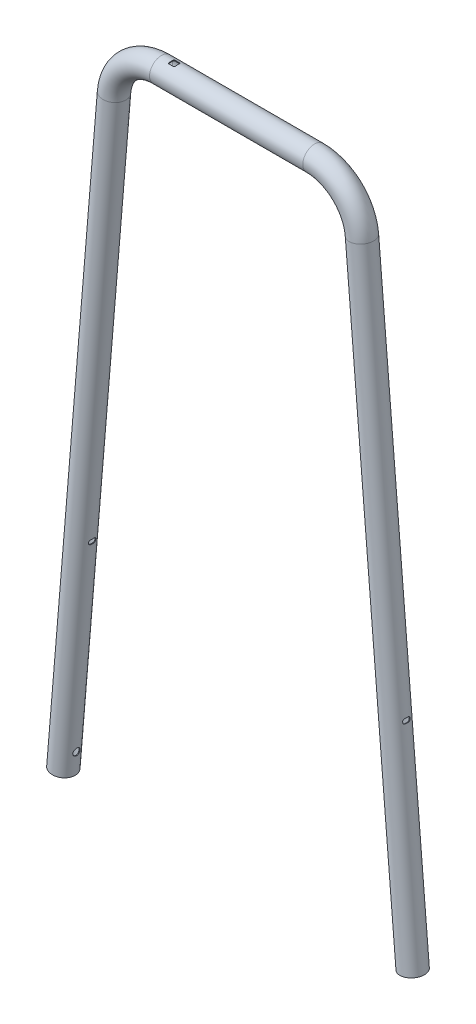
SolidWorks part; units mm, degrees
ref_plane "Front Plane" through (0, 0, 0) normal (0, 0, 1) x (1, 0, 0)
ref_plane "Top Plane" through (0, 0, 0) normal (0, 1, 0) x (1, 0, 0)
ref_plane "Right Plane" through (0, 0, 0) normal (1, 0, 0) x (0, 0, -1)
sketch "Sketch1" plane through (0, 0, 0) normal (0, 0, 1) x (1, 0, 0)
  line L0 (0, 0) -> (0, 595.2821) construction
  line L1 (0, 0) -> (414.971, 0) construction
  line L2 (-85.4711, 567.016) -> (85.4711, 567.016)
  line L3 (138.2891, 518.4048) -> (194.85, -162.284)
  line L4 (-138.2891, 518.4048) -> (-194.85, -162.284)
  line L5 (-194.85, -162.284) -> (-299.6948, -162.284) construction
  arc A0 (138.2891, 518.4048) -> (85.4711, 567.016) centre (85.4711, 514.016) ccw
  arc A1 (-138.2891, 518.4048) -> (-85.4711, 567.016) centre (-85.4711, 514.016) cw
  point P12 (134.2498, 567.016)
  point P17 (0, 567.016)
  dimension "D4" = 53
  dimension "D1" = 389.7
  dimension "D2" = 9.5
  dimension "D3" = 729.3
ref_plane "Plane1" through (-194.85, -162.284, 0) normal (-0.0828, -0.9966, 0) x (-0.9966, 0.0828, 0)
sketch "Sketch2" plane through (-194.85, -162.284, 0) normal (-0.0828, -0.9966, 0) x (-0.9966, 0.0828, 0)
  circle A0 centre (0, 0) radius 13.2
  circle A1 centre (0, 0) radius 12.4
  dimension "D1" = 0.8
  dimension "D2" = 26.4
sweep "Sweep2" add profiles "Sketch2" path "Sketch1"
sketch "Sketch6" plane through (-14.7284, -177.251, 0) normal (-0.0828, -0.9966, 0) x (0.9966, -0.0828, 0)
  line L0 (-180.7423, 0) -> (-193.1423, 0)
  line L1 (-180.7423, 0) -> (-180.7423, 12.4)
  circle A0 centre (-180.7423, 0) radius 12.4 construction
  circle A1 centre (-180.7423, 0) radius 12.4 construction
ref_plane "Plane3" through (-194.85, -162.284, 0) normal (-0.9966, 0.0828, 0) x (0, 0, 1)
ref_plane "Plane4" through (0, 580.216, 0) normal (0, 1, 0) x (1, 0, 0)
sketch "Sketch17" plane through (-194.85, -162.284, 0) normal (-0.9966, 0.0828, 0) x (0, 0, 1)
  line L0 (0, 0) -> (0, 23.8) construction
  line L1 (-13.2, 0) -> (13.2, 0) construction
  line L2 (0, 23.8) -> (0, 236.8) construction
  circle A0 centre (0, 23.8) radius 4
  dimension "D3" = 8
  dimension "D1" = 23.8
  dimension "D2" = 236.8
extrude "Cut-Extrude6" cut sketch "Sketch17" against normal blind 50
sketch "Sketch18" plane through (-194.85, -162.284, 0) normal (-0.9966, 0.0828, 0) x (0, 0, 1)
  line L0 (0, 0) -> (0, 236.8) construction
  line L1 (-12.4, 0) -> (12.4, 0) construction
  line L3 (-2, 239.3) -> (2, 239.3)
  line L4 (-4, 237.3) -> (-4, 236.3)
  line L5 (-2, 234.3) -> (2, 234.3)
  line L6 (4, 237.3) -> (4, 236.3)
  line L7 (-4, 239.3) -> (4, 234.3) construction
  line L8 (-4, 234.3) -> (4, 239.3) construction
  arc A0 (-2, 234.3) -> (-4, 236.3) centre (-2, 236.3) cw
  arc A1 (4, 236.3) -> (2, 234.3) centre (2, 236.3) cw
  arc A2 (2, 239.3) -> (4, 237.3) centre (2, 237.3) cw
  arc A3 (-2, 239.3) -> (-4, 237.3) centre (-2, 237.3) ccw
  dimension "D3" = 2
  dimension "D1" = 5
  dimension "D2" = 8
  dimension "D4" = 236.8
extrude "Cut-Extrude7" cut sketch "Sketch18" against normal blind 50 and the other way blind 50
mirror "Mirror2" about plane through (0, 0, 0) normal (1, 0, 0) of "Cut-Extrude6", "Cut-Extrude7"
sketch "Sketch19" plane through (-194.85, -162.284, 0) normal (-0.9966, 0.0828, 0) x (0, 0, 1)
  line L0 (0, 0) -> (0, 496.8) construction
  line L1 (-12.4, 0) -> (12.4, 0) construction
  circle A0 centre (0, 496.8) radius 4
  dimension "D1" = 496.8
extrude "Cut-Extrude8" cut sketch "Sketch19" along normal blind 50
sketch "Sketch20" plane through (0, 580.216, 0) normal (0, 1, 0) x (1, 0, 0)
  line L0 (-208.0047, 0) -> (-70.9891, 0) construction
  circle A0 centre (-70.9891, 0) radius 3.5
  ellipse E0 centre (-194.85, 0) end of major axis (-194.85, 13.2) minor radius 13.1547 construction
  ellipse E1 centre (-138.2891, 0) end of major axis (-138.2891, 13.2) minor radius 13.1547 construction
  dimension "D2" = 7
  dimension "D1" = 67.3
extrude "Cut-Extrude9" cut sketch "Sketch20" against normal blind 50
sketch "Sketch21" plane through (0, 580.216, 0) normal (0, 1, 0) x (1, 0, 0)
  line L0 (-208.0047, 0) -> (-70.9891, 0) construction
  line L2 (-73.4891, -3.5) -> (-68.4891, -3.5)
  line L3 (-74.4891, -2.5) -> (-74.4891, 2.5)
  line L4 (-73.4891, 3.5) -> (-68.4891, 3.5)
  line L5 (-67.4891, -2.5) -> (-67.4891, 2.5)
  line L6 (-74.4891, -3.5) -> (-67.4891, 3.5) construction
  line L7 (-74.4891, 3.5) -> (-67.4891, -3.5) construction
  arc A0 (-73.4891, 3.5) -> (-74.4891, 2.5) centre (-73.4891, 2.5) ccw
  arc A1 (-74.4891, -2.5) -> (-73.4891, -3.5) centre (-73.4891, -2.5) ccw
  arc A2 (-68.4891, 3.5) -> (-67.4891, 2.5) centre (-68.4891, 2.5) cw
  arc A3 (-67.4891, -2.5) -> (-68.4891, -3.5) centre (-68.4891, -2.5) cw
  ellipse E0 centre (-194.85, 0) end of major axis (-194.85, 13.2) minor radius 13.1547 construction
  dimension "D3" = 1
  dimension "D4" = 1
  dimension "D1" = 7
  dimension "D2" = 7
extrude "Cut-Extrude10" cut sketch "Sketch21" against normal blind 10
